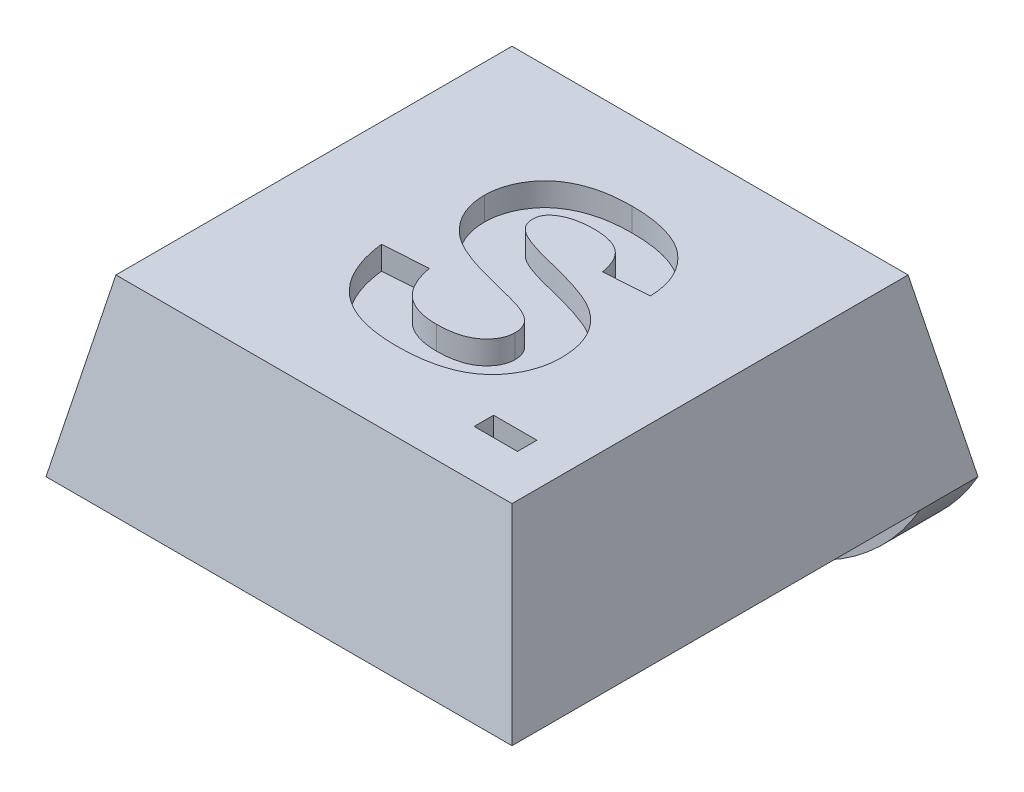
SolidWorks part; units mm, degrees
ref_plane "Front Plane" through (0, 0, 0) normal (0, 0, 1) x (1, 0, 0)
ref_plane "Top Plane" through (0, 0, 0) normal (0, 1, 0) x (1, 0, 0)
ref_plane "Right Plane" through (0, 0, 0) normal (1, 0, 0) x (0, 0, -1)
sketch "Sketch1" plane through (0, 0, 0) normal (0, 1, 0) x (1, 0, 0)
  line L1 (0, 0) -> (8, 0)
  line L2 (0, 0) -> (0, 8)
  line L3 (0, 8) -> (8, 8)
  line L4 (8, 0) -> (8, 8)
  dimension "D1" = 8
  dimension "D2" = 8
extrude "Boss-Extrude1" add sketch "Sketch1" along normal blind 3
sketch "Sketch2" plane through (0, 0, 0) normal (0, 0, 1) x (1, 0, 0)
  line L0 (0, 0) -> (0.6, 3)
  line L1 (0, 3) -> (8, 3) construction
  line L2 (0.6, 3) -> (0, 3)
  line L3 (0, 3) -> (0, 0)
  line L4 (8, 0) -> (7.4, 3)
  line L5 (7.4, 3) -> (8, 3)
  line L6 (8, 3) -> (8, 0)
  dimension "D1" = 0.6
  dimension "D2" = 0.6
extrude "Cut-Extrude1" cut sketch "Sketch2" against normal through all both and the other way through all
sketch "Sketch3" plane through (0, 0, 0) normal (1, 0, 0) x (0, 0, -1)
  line L0 (0, 0) -> (0.6, 3)
  line L1 (8, 3) -> (0, 3) construction
  line L2 (0.6, 3) -> (0, 3)
  line L3 (0, 3) -> (0, 0)
  line L4 (8, 3) -> (7.4, 3)
  line L5 (7.4, 3) -> (8, 0)
  line L6 (8, 3) -> (8, 0)
  dimension "D1" = 0.6
  dimension "D2" = 0.6
extrude "Cut-Extrude2" cut sketch "Sketch3" along normal blind 11
sketch "Sketch4" plane through (0, 0, 0) normal (0, -1, 0) x (1, 0, 0)
  line L0 (8, 0) -> (8, -8) construction
  line L3 (0, 0) -> (8, 0) construction
  circle A0 centre (4, -3.75) radius 1.8
  dimension "D1" = 3.6
  dimension "D2" = 4
  dimension "D3" = 3.75
extrude "Cut-Extrude3" cut sketch "Sketch4" against normal blind 0.8
sketch "Sketch5" plane through (0, 0, 0) normal (0, -1, 0) x (1, 0, 0)
  line L0 (8, 0) -> (8, -8) construction
  line L1 (0, -8) -> (8, -8)
  line L2 (0, -8) -> (0, -7)
  line L3 (0, -7) -> (8, -7)
  line L4 (8, -8) -> (8, -7)
  dimension "D1" = 1
extrude "Boss-Extrude2" add sketch "Sketch5" along normal blind 2
fillet "Fillet1" radius 4 2 edges at (8, -2, -7.5) (0, -2, -7.5)
sketch "Sketch6" plane through (0, 3, 0) normal (0, 1, 0) x (1, 0, 0)
  text T0 "S" font "Arial" height 4
extrude "Cut-Extrude4" cut sketch "Sketch6" against normal blind 0.4
sketch "Sketch7" plane through (0, 3, 0) normal (0, 1, 0) x (1, 0, 0)
  text T0 "-" font "Arial" height 2
extrude "Cut-Extrude5" cut sketch "Sketch7" against normal blind 0.4
